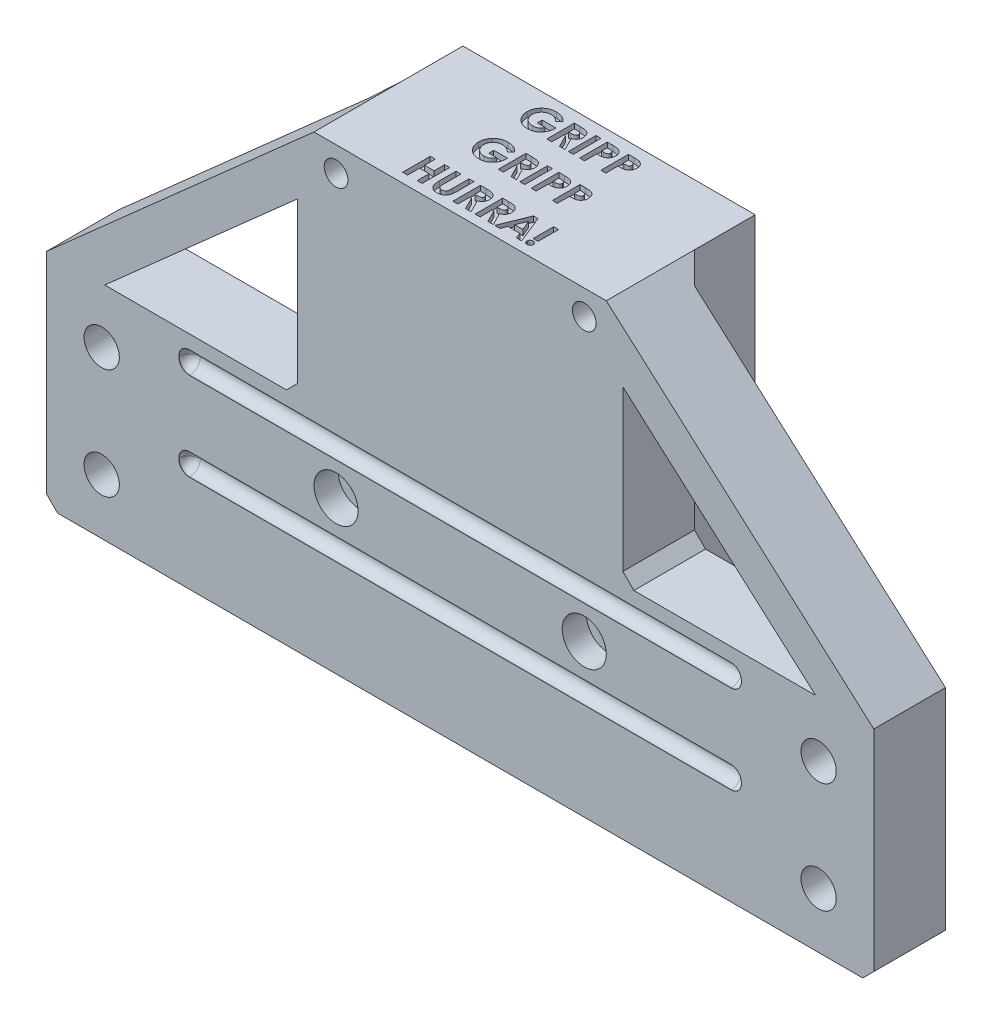
SolidWorks part; units mm, degrees
material "ABS"
ref_plane "Ebene vorne" through (0, 0, 0) normal (0, 0, 1) x (1, 0, 0)
ref_plane "Ebene oben" through (0, 0, 0) normal (0, 1, 0) x (1, 0, 0)
ref_plane "Ebene rechts" through (0, 0, 0) normal (1, 0, 0) x (0, 0, -1)
sketch "Skizze1" plane through (0, 0, 0) normal (0, 0, 1) x (1, 0, 0)
  line L1 (-75, -20.05) -> (75, -20.05)
  line L2 (-75, -20.05) -> (-75, 20.05)
  line L3 (-75, 20.05) -> (75, 20.05)
  line L4 (75, -20.05) -> (75, 20.05)
  line L5 (-75, -20.05) -> (75, 20.05) construction
  line L6 (-75, 20.05) -> (75, -20.05) construction
  point P0 (0, 0)
  dimension "D1" = 40.1
  dimension "D2" = 150
extrude "Aufsatz-Linear austragen1" add sketch "Skizze1" along normal blind 13
sketch "Skizze2" plane through (0, 0, 0) normal (0, 0, -1) x (-1, 0, 0)
  line L1 (65, -10) -> (-65, -10)
  line L2 (65, -10) -> (65, 10)
  line L3 (65, 10) -> (-65, 10)
  line L4 (-65, -10) -> (-65, 10)
  line L5 (65, -10) -> (-65, 10) construction
  line L6 (65, 10) -> (-65, -10) construction
  point P0 (0, 0)
  point P6 (65, 0)
  point P7 (-65, 0)
  dimension "D1" = 20
  dimension "D2" = 130
hole_wizard "M6 Clearance Hole1" positions "3D-Skizze1" profile "Skizze3" hole size "M6" standard "ISO" end condition through all
sketch3d "3D-Skizze1"
  point P0 (65, -10, 0)
  point P3 (-65, 10, 0)
sketch "Skizze3" plane through (65, -10, 0) normal (1, 0, 0) x (0, 1, 0)
  line L0 (0, 0) -> (0, 13)
  line L1 (0, 13) -> (3.2, 13)
  line L2 (3.2, 13) -> (3.2, 0)
  line L5 (3.2, 0) -> (0, 0)
  line L11 (0, -6.35) -> (0, 107.95) construction
  dimension "Bohrerdurchmesser" = 6.4
  dimension "Bohrungstiefe" = 13
hole_wizard "M6 Clearance Hole2" positions "Skizze4" profile "Skizze5" hole size "M6" standard "DIN" end condition through all
sketch "Skizze4" plane through (0, 0, 0) normal (0, 0, -1) x (-1, 0, 0)
  point P0 (-65, 10)
  point P3 (65, -10)
sketch "Skizze5" plane through (65, 10, 0) normal (1, 0, 0) x (0, 1, 0)
  line L0 (0, 0) -> (0, 13)
  line L1 (0, 13) -> (3.2, 13)
  line L2 (3.2, 13) -> (3.2, 0)
  line L5 (3.2, 0) -> (0, 0)
  line L11 (0, -6.35) -> (0, 107.95) construction
  dimension "Bohrerdurchmesser" = 6.4
  dimension "Bohrungstiefe" = 13
sketch "Skizze6" plane through (0, 0, 13) normal (0, 0, 1) x (1, 0, 0)
  line L0 (75, 20.05) -> (-75, 20.05) construction
  line L1 (-26.5, 0) -> (26.5, 0)
  line L2 (-26.5, 0) -> (-26.5, 63.05)
  line L3 (-26.5, 63.05) -> (26.5, 63.05)
  line L4 (26.5, 0) -> (26.5, 63.05)
  dimension "D1" = 63.05
  dimension "D2" = 26.5
  dimension "D3" = 53
  dimension "D4" = 20.05
extrude "Aufsatz-Linear austragen2" add sketch "Skizze6" against normal blind 27
sketch "Skizze7" plane through (0, 0, 13) normal (0, 0, 1) x (1, 0, 0)
  line L0 (26.5, 63.05) -> (-26.5, 63.05) construction
  line L1 (-22.5, 58.55) -> (22.5, 58.55)
  line L2 (-22.5, 58.55) -> (-22.5, 7.55)
  line L3 (-22.5, 7.55) -> (22.5, 7.55)
  line L4 (22.5, 58.55) -> (22.5, 7.55)
  dimension "D1" = 45
  dimension "D2" = 51
  dimension "D3" = 22.5
  dimension "D4" = 4.5
sketch "Skizze11" plane through (-26.5, 0, 0) normal (-1, 0, 0) x (0, 0, 1)
  line L0 (-14, 63.05) -> (-14, 0) construction
  line L1 (0, 0) -> (-14, 0)
  line L2 (0, 0) -> (0, 3.05)
  line L3 (0, 3.05) -> (-14, 3.05)
  line L4 (-14, 0) -> (-14, 3.05)
  line L5 (-14, 63.05) -> (13, 63.05) construction
  dimension "D1" = 60
extrude "Schnitt-Linear austragen2" cut sketch "Skizze11" against normal through all and the other way through all
sketch "Skizze12" plane through (0, 0, 13) normal (0, 0, 1) x (1, 0, 0)
  line L0 (-75, 20.05) -> (-26.5, 63.05)
  line L1 (-26.5, 63.05) -> (-26.5, 20.05)
  line L2 (-26.5, 20.05) -> (-75, 20.05)
extrude "Aufsatz-Linear austragen3" add sketch "Skizze12" against normal blind 13
mirror "Spiegeln1" about plane through (0, 0, 0) normal (1, 0, 0) of "Aufsatz-Linear austragen3"
hole_wizard "CBORE for M4 Hex Socket Head Cap Screw2" positions "Sketch3" profile "Sketch4" counterbore size "M4" standard "ISO" end condition through all
sketch "Sketch3" plane through (0, 0, 13) normal (0, 0, 1) x (1, 0, 0)
  point P0 (-22.5, 7.55)
  point P3 (22.5, 7.55)
sketch "Sketch4" plane through (-22.5, 7.55, 13) normal (1, 0, 0) x (0, -1, 0)
  line L0 (0, 0) -> (0, 27)
  line L1 (0, 27) -> (2.25, 27)
  line L3 (2.25, 27) -> (2.25, 4.4)
  line L4 (2.25, 4.4) -> (4, 4.4)
  line L5 (4, 4.4) -> (4, 0)
  line L7 (4, 0) -> (0, 0)
  line L11 (0, -6.35) -> (0, 107.95) construction
  dimension "Thru Hole Dia." = 4.5
  dimension "Thru Hole Depth" = 27
  dimension "C'Bore Dia." = 8
  dimension "C'Bore Depth" = 4.4
hole_wizard "M4 Clearance Hole1" positions "Sketch5" profile "Sketch6" hole size "M4" standard "ISO" end condition through all
sketch "Sketch5" plane through (0, 0, 13) normal (0, 0, 1) x (1, 0, 0)
  point P0 (-22.5, 58.55)
  point P3 (22.5, 58.55)
sketch "Sketch6" plane through (-22.5, 58.55, 13) normal (1, 0, 0) x (0, -1, 0)
  line L0 (0, 0) -> (0, 27)
  line L1 (0, 27) -> (2.15, 27)
  line L2 (2.15, 27) -> (2.15, 0)
  line L5 (2.15, 0) -> (0, 0)
  line L11 (0, -6.35) -> (0, 107.95) construction
  dimension "Thru Hole Dia." = 4.3
  dimension "Thru Hole Depth" = 27
sketch "Sketch7" plane through (0, 0, 13) normal (0, 0, 1) x (1, 0, 0)
  line L0 (-64.4484, 20.05) -> (-29.5, 51.0352)
  line L1 (-29.5, 51.0352) -> (-29.5, 20.05)
  line L2 (-29.5, 20.05) -> (-64.4484, 20.05)
  line L4 (-26.5, 63.05) -> (-75, 20.05) construction
  dimension "D1" = 7
  dimension "D2" = 0
  dimension "D3" = 3
extrude "Cut-Extrude1" cut sketch "Sketch7" against normal blind 15
mirror "Mirror1" about plane through (0, 0, 0) normal (1, 0, 0) of "Cut-Extrude1"
chamfer "Chamfer1" distance 3 angle 45 2 edges at (26.5, 33.05, 0) (-26.5, 33.05, 0)
chamfer "Chamfer2" distance 2 angle 45 2 edges at (29.5, 20.05, 6.5) (-29.5, 20.05, 6.5)
chamfer "Chamfer3" distance 2 angle 45 2 edges at (75, -20.05, 6.5) (-75, -20.05, 6.5)
sketch "Sketch8" plane through (0, 0, 13) normal (0, 0, 1) x (1, 0, 0)
  line L0 (-22.5, 7.55) -> (22.5, 7.55) construction
  line L1 (-49.1, 1.55) -> (49.1, 1.55)
  line L2 (-51, -0.35) -> (-51, -0.55)
  line L3 (-49.1, -2.45) -> (49.1, -2.45)
  line L4 (51, -0.35) -> (51, -0.55)
  line L5 (-49.1, 17.55) -> (49.1, 17.55)
  line L6 (51, 15.45) -> (51, 15.65)
  line L7 (-49.1, 13.55) -> (49.1, 13.55)
  line L8 (-51, 15.45) -> (-51, 15.65)
  circle A3 centre (-22.5, 7.55) radius 2.25 construction
  arc A4 (51, -0.55) -> (49.1, -2.45) centre (49.1, -0.55) cw
  arc A5 (51, -0.35) -> (49.1, 1.55) centre (49.1, -0.35) ccw
  arc A6 (51, 15.45) -> (49.1, 13.55) centre (49.1, 15.45) cw
  arc A7 (51, 15.65) -> (49.1, 17.55) centre (49.1, 15.65) ccw
  arc A8 (-51, -0.55) -> (-49.1, -2.45) centre (-49.1, -0.55) ccw
  arc A9 (-51, -0.35) -> (-49.1, 1.55) centre (-49.1, -0.35) cw
  arc A10 (-51, 15.65) -> (-49.1, 17.55) centre (-49.1, 15.65) cw
  arc A11 (-51, 15.45) -> (-49.1, 13.55) centre (-49.1, 15.45) ccw
  point P17 (51, -2.45)
  point P20 (51, 1.55)
  point P23 (51, 13.55)
  point P26 (51, 17.55)
  point P29 (-51, -2.45)
  point P32 (-51, 1.55)
  point P35 (-51, 17.55)
  point P38 (-51, 13.55)
  dimension "D4" = 6
  dimension "D6" = 1.9
  dimension "D7" = 1.9
  dimension "D1" = 102
  dimension "D2" = 51
  dimension "D3" = 4
  dimension "D5" = 12
extrude "Cut-Extrude2" cut sketch "Sketch8" against normal blind 2
fillet "Fillet1" radius 1.9 16 edges at (0, -2.45, 11) (-50.4435, -1.8935, 11) (-51, -0.45, 11) (-50.4435, 0.9935, 11) (0, 1.55, 11) (50.4435, 0.9935, 11) (51, -0.45, 11) (50.4435, -1.8935, 11) (0, 13.55, 11) (-50.4435, 14.1065, 11) (-51, 15.55, 11) (-50.4435, 16.9935, 11) (0, 17.55, 11) (50.4435, 16.9935, 11) (51, 15.55, 11) (50.4435, 14.1065, 11)
sketch "Sketch9" plane through (0, 63.05, 0) normal (0, 1, 0) x (1, 0, 0)
  line L4 (-20.5805, 7) -> (19.376, 7) construction
  line L5 (26.5, 14) -> (-26.5, 14) construction
  text T0 "<b>GRIPP</b>\r\n<b>GRIPP</b>\r\n<b>HURRA!</b>" font "Century Gothic" height 5
  dimension "D1" = 7
extrude "Cut-Extrude3" cut sketch "Sketch9" against normal blind 1
